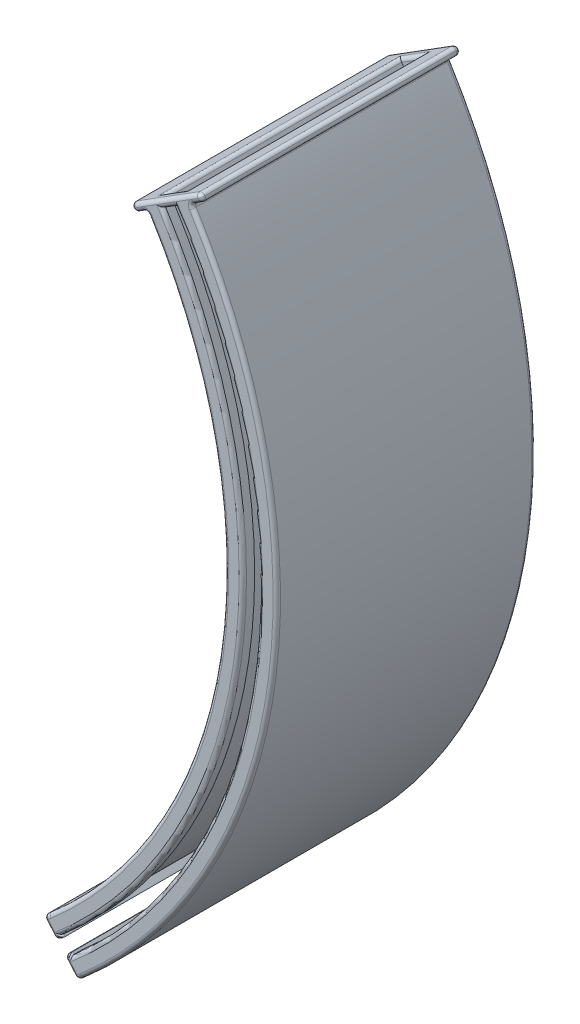
SolidWorks part; units mm, degrees
ref_plane "Front Plane" through (0, 0, 0) normal (0, 0, 1) x (1, 0, 0)
ref_plane "Top Plane" through (0, 0, 0) normal (0, 1, 0) x (1, 0, 0)
ref_plane "Right Plane" through (0, 0, 0) normal (1, 0, 0) x (0, 0, -1)
ref_plane "Plane1" through (-17.5, 0, 0) normal (1, 0, 0) x (0, 0, -1)
ref_plane "Plane2" through (-35, 0, 0) normal (1, 0, 0) x (0, 0, -1)
sketch "Sketch1" plane through (-17.5, 0, 0) normal (1, 0, 0) x (0, 0, -1)
  line L0 (0, 0) -> (0, -50) construction
  dimension "D1" = 50
sketch "Sketch2" plane through (0, 0, 0) normal (1, 0, 0) x (0, 0, -1)
  point P0 (0, 0)
sketch "Sketch3" plane through (-35, 0, 0) normal (1, 0, 0) x (0, 0, -1)
  point P0 (0, 0)
sketch "Sketch4" plane through (0, 0, 0) normal (0, 0, 1) x (1, 0, 0)
  line L0 (-17.5, 0) -> (-17.5, -50) construction
  arc A0 (9.9992, -0.126) -> (-45, -0.1273) centre (-17.5, -17.4818) cw construction
  arc A1 (9.9992, -0.126) -> (3.7287, -42.1146) centre (-17.5, -17.4818) cw construction
  arc A2 (11.7239, 0.8866) -> (5.0823, -43.587) centre (-17.5, -17.4818) cw construction
  dimension "D1" = 10
  dimension "D3" = 32.5182
  dimension "D4" = 46.2567
  dimension "D5" = 2
  dimension "D7" = 48.972
  dimension "D2" = 10
  dimension "D6" = 2
sketch "Sketch6" plane through (0, 0, 0) normal (0, 0, 1) x (1, 0, 0)
  line L0 (15.0182, 10) -> (15.0182, -39.6825) construction
  arc A0 (3.7287, -42.1146) -> (9.9992, -0.126) centre (-17.5, -17.4818) ccw construction
  dimension "D1" = 32.5182
ref_plane "Plane3" through (15.0182, 0, 0) normal (1, 0, 0) x (0, 0, -1)
sketch "Sketch7" plane through (0, 0, 0) normal (0, 0, 1) x (1, 0, 0)
  arc A0 (11.7239, 0.8866) -> (5.0823, -43.587) centre (-17.5, -17.4818) cw
sketch "Sketch8" plane through (0, 0, 0) normal (0, 0, 1) x (1, 0, 0)
  line L0 (17.0172, 0) -> (17.0172, -35.7055) construction
  arc A1 (5.0823, -43.587) -> (11.7239, 0.8866) centre (-17.5, -17.4818) ccw construction
ref_plane "Plane4" through (17.0172, 0, 0) normal (1, 0, 0) x (0, 0, -1)
sketch "Sketch9" plane through (17.0172, 0, 0) normal (1, 0, 0) x (0, 0, -1)
  line L0 (31.6795, -17.4818) -> (-12.7941, -17.4818) construction
  line L1 (0, 0.8866) -> (0, -43.587) construction
  dimension "D1" = 0
ref_plane "Plane5" through (0, -17.4818, 0) normal (0, 1, 0) x (1, 0, 0)
sketch "Sketch10" plane through (0, -17.4818, 0) normal (0, 1, 0) x (1, 0, 0)
  line L0 (17.0172, 31.6795) -> (17.0172, -12.7941) construction
  line L1 (17.0172, 8.75) -> (20.5172, 8.75)
  line L2 (17.0172, 8.75) -> (17.0172, -8.75)
  line L3 (17.0172, -8.75) -> (20.5172, -8.75)
  line L4 (20.5172, 8.75) -> (20.5172, -8.75)
  line L5 (5.0823, 0) -> (17.0172, 0) construction
  dimension "D1" = 17.5
  dimension "D2" = 3.5
  dimension "D3" = 8.75
sweep "Sweep1" add profiles "Sketch10" path "Sketch7"
shell "Shell1" thickness 0.8
sketch "Sketch11" plane through (2.9206, -4.6466, 0) normal (-0.5322, 0.8466, 0) x (0.8466, 0.5322, 0)
  line L0 (10.3978, -8.75) -> (13.8978, -8.75) construction
  line L1 (14.8978, 8.75) -> (9.3978, 8.75)
  line L2 (14.8978, 8.75) -> (14.8978, -8.75)
  line L3 (14.8978, -8.75) -> (9.3978, -8.75)
  line L4 (9.3978, 8.75) -> (9.3978, -8.75)
  line L5 (13.0978, 7.95) -> (11.1978, 7.95)
  line L6 (13.0978, 7.95) -> (13.0978, -7.95)
  line L7 (13.0978, -7.95) -> (11.1978, -7.95)
  line L8 (11.1978, 7.95) -> (11.1978, -7.95)
  line L9 (13.8978, -8.75) -> (13.8978, 8.75) construction
  dimension "D1" = 17.5
  dimension "D2" = 5.5
  dimension "D3" = 0
  dimension "D4" = 1
extrude "Boss-Extrude1" add sketch "Sketch11" along normal blind 0.5
sketch "Sketch12" plane through (-18.6595, -16.1414, 0) normal (-0.7563, -0.6542, 0) x (0, 0, 1)
  line L0 (-7.95, -37.0895) -> (7.95, -37.0895) construction
  line L1 (-8.75, -36.2895) -> (8.75, -36.2895)
  line L2 (-8.75, -36.2895) -> (-8.75, -39.7895)
  line L3 (-8.75, -39.7895) -> (8.75, -39.7895)
  line L4 (8.75, -36.2895) -> (8.75, -39.7895)
  line L5 (-8.75, -37.6395) -> (8.75, -37.6395)
  line L6 (-8.75, -37.6395) -> (-8.75, -38.4395)
  line L7 (-8.75, -38.4395) -> (8.75, -38.4395)
  line L8 (8.75, -37.6395) -> (8.75, -38.4395)
  line L9 (-7.95, -37.6395) -> (-7.95, -38.4395)
  line L10 (-8.75, -36.2895) -> (8.75, -36.2895)
  line L11 (-8.75, -36.2895) -> (-8.75, -37.6395)
  line L12 (-8.75, -37.6395) -> (8.75, -37.6395)
  line L13 (8.75, -36.2895) -> (8.75, -37.6395)
  line L14 (8.75, -39.7895) -> (-8.75, -39.7895)
  line L15 (8.75, -39.7895) -> (8.75, -38.4395)
  line L16 (8.75, -38.4395) -> (-8.75, -38.4395)
  line L17 (-8.75, -39.7895) -> (-8.75, -38.4395)
  line L18 (-7.95, -38.9895) -> (-7.95, -37.0895) construction
  line L19 (7.95, -37.6395) -> (7.95, -38.4395)
  line L20 (7.95, -37.0895) -> (7.95, -38.9895) construction
  line M3 (-7.95, -38.9895) -> (-7.95, -37.0895)
  line M4 (-7.95, -37.0895) -> (7.95, -37.0895)
  line M5 (7.95, -37.0895) -> (7.95, -38.9895)
  line M6 (7.95, -38.9895) -> (-7.95, -38.9895)
  line M7 (8.75, -36.2895) -> (-8.75, -36.2895)
  line M8 (-8.75, -36.2895) -> (-8.75, -39.7895)
  line M9 (-8.75, -39.7895) -> (8.75, -39.7895)
  line M10 (8.75, -39.7895) -> (8.75, -36.2895)
  dimension "D1" = 0.8
  dimension "D2" = 0.55
extrude "Boss-Extrude2" add sketch "Sketch12" along normal blind 0.5 contours L5 L4 M8 M3 M4 M5 M7 | L5 M3 M5 M4 | L7 M3 M6 M5 | L7 M8 M9 M10 M5 M6 M3
sketch "Sketch13" plane through (0, 0, 8.75) normal (0, 0, 1) x (1, 0, 0)
  line L0 (6.9939, -46.5611) -> (6.1107, -45.5401) construction
  line L1 (11.7239, 0.8866) -> (12.7399, 1.5252)
  line L2 (10.6112, 0.7778) -> (15.2677, 3.7046) construction
  line L3 (13.6712, 2.1106) -> (14.6872, 2.7491)
  line L4 (12.7399, 1.5252) -> (13.6712, 2.1106)
  line L5 (6.587, -45.3264) -> (5.8673, -44.4945)
  arc A0 (5.4869, -44.819) -> (12.7399, 1.5252) centre (-17.5, -17.4818) ccw
  arc A1 (6.2066, -45.651) -> (13.6712, 2.1106) centre (-17.5, -17.4818) ccw
  arc A2 (5.0823, -43.587) -> (11.7239, 0.8866) centre (-17.5, -17.4818) ccw construction
  arc A4 (7.3721, -46.234) -> (14.6872, 2.7491) centre (-17.5, -17.4818) ccw construction
  dimension "D1" = 1.2
  dimension "D2" = 1.2
extrude "Cut-Extrude1" cut sketch "Sketch13" against normal through all both and the other way through all contours L5 A1 L4 A0
fillet "Fillet1" radius 0.25 46 edges at (15.5338, 3.2813, 0) (14.6872, 2.7491, 0) (10.8772, 0.3544, 0) (11.7239, 0.8866, 0) (12.9394, 2.2412, -7.95) (12.1351, 1.7356, 0) (12.9394, 2.2412, 7.95) (13.7438, 2.7467, 0) (10.6112, 0.7778, 0) (15.2677, 3.7046, 0) (13.2055, 1.8179, -8.75) (18.9134, -22.9198, -8.75) (6.5379, -45.2697, -8.75) (6.2998, -45.3765, -8.75) (6.1107, -45.5401, 0) (6.2998, -45.3765, 8.75) (7.183, -46.3975, 8.75) (7.183, -46.3975, -8.75) (20.1002, -23.097, -8.75) (20.1002, -23.097, 8.75) (15.1105, 3.0152, -8.75) (12.9394, 2.2412, -8.75) (11.3006, 0.6205, -8.75) (16.6386, -22.5801, 8.75) (16.6386, -22.5801, -8.75) (4.8932, -43.7505, -8.75) (4.8932, -43.7505, 8.75) (5.7764, -44.7715, 8.75) (5.5873, -44.9351, 0) (5.7764, -44.7715, -8.75) (5.9164, -44.5512, -8.75) (17.8254, -22.7573, -8.75) (6.9939, -46.5611, 0) (6.5523, -46.0506, -8.75) (6.5523, -46.0506, 8.75) (4.7041, -43.9141, 0) (5.1457, -44.4246, -8.75) (5.1457, -44.4246, 8.75) (11.3006, 0.6205, 8.75) (12.9394, 2.2412, 8.75) (15.1105, 3.0152, 8.75)
